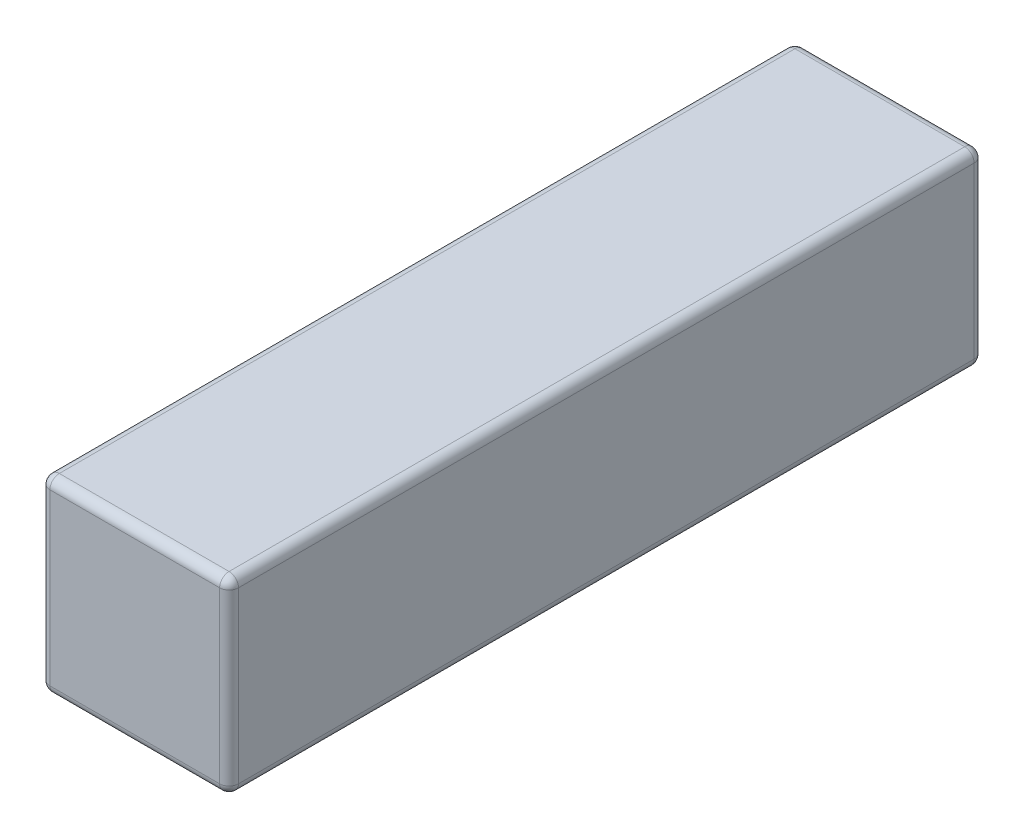
SolidWorks part; units mm, degrees
ref_plane "Front Plane" through (0, 0, 0) normal (0, 0, 1) x (1, 0, 0)
ref_plane "Top Plane" through (0, 0, 0) normal (0, 1, 0) x (1, 0, 0)
ref_plane "Right Plane" through (0, 0, 0) normal (1, 0, 0) x (0, 0, -1)
sketch "Sketch1" plane through (0, 0, 0) normal (0, 0, 1) x (1, 0, 0)
  line L3 (1.5, -1.5) -> (-1.5, -1.5)
  line L4 (1.5, -1.5) -> (1.5, 1.5)
  line L5 (1.5, 1.5) -> (-1.5, 1.5)
  line L6 (-1.5, -1.5) -> (-1.5, 1.5)
  line L7 (1.5, -1.5) -> (-1.5, 1.5) construction
  line L8 (1.5, 1.5) -> (-1.5, -1.5) construction
  point P0 (0, 0)
  dimension "Width" = 3
  dimension "Height" = 3
sketch "Sketch2" plane through (0, 0, 0) normal (1, 0, 0) x (0, 0, -1)
  line L2 (6, -1.5) -> (-6, -1.5)
  line L3 (6, -1.5) -> (6, 1.5)
  line L4 (6, 1.5) -> (-6, 1.5)
  line L5 (-6, -1.5) -> (-6, 1.5)
  line L6 (6, -1.5) -> (-6, 1.5) construction
  line L7 (6, 1.5) -> (-6, -1.5) construction
  point P0 (0, 0)
  point P4 (0, 0)
  dimension "Length" = 12
sketch "Sketch3" plane through (0, 0, 0) normal (0, 0, 1) x (1, 0, 0)
  line L0 (1.5, -1.5) -> (1.5, 1.5) construction
  line L5 (1.5, -1.5) -> (-1.5, -1.5) construction
  line L6 (-1.5, -1.5) -> (-1.5, 1.5) construction
  line L7 (1.5, 1.5) -> (-1.5, 1.5) construction
  line L8 (1.5, -1.5) -> (1.5, 1.5)
  line L9 (1.5, -1.5) -> (-1.5, -1.5)
  line L10 (-1.5, -1.5) -> (-1.5, 1.5)
  line L11 (1.5, 1.5) -> (-1.5, 1.5)
extrude "Boss-Extrude1" add sketch "Sketch3" along normal up to vertex (6 mm away) and the other way up to vertex (6 mm away) up to point (0, 1.5, 6) other way up to point (0, 1.5, -6)
fillet "Fillet2" radius 0.15 12 edges at (-1.5, 0, -6) (0, -1.5, -6) (-1.5, 1.5, 0) (0, 1.5, -6) (1.5, 1.5, 0) (1.5, 0, -6) (1.5, -1.5, 0) (-1.5, 0, 6) (0, 1.5, 6) (1.5, 0, 6) (0, -1.5, 6) (-1.5, -1.5, 0)
ref_plane "Contact Plane 1" through (0, 0, 6) normal (0, 0, 1) x (1, 0, 0)
ref_plane "Contact Plane 2" through (0, 0, -6) normal (0, 0, 1) x (1, 0, 0)
ref_axis "Center Axis 1" through (0, 0, -4.4) along (0, 0, 1)
